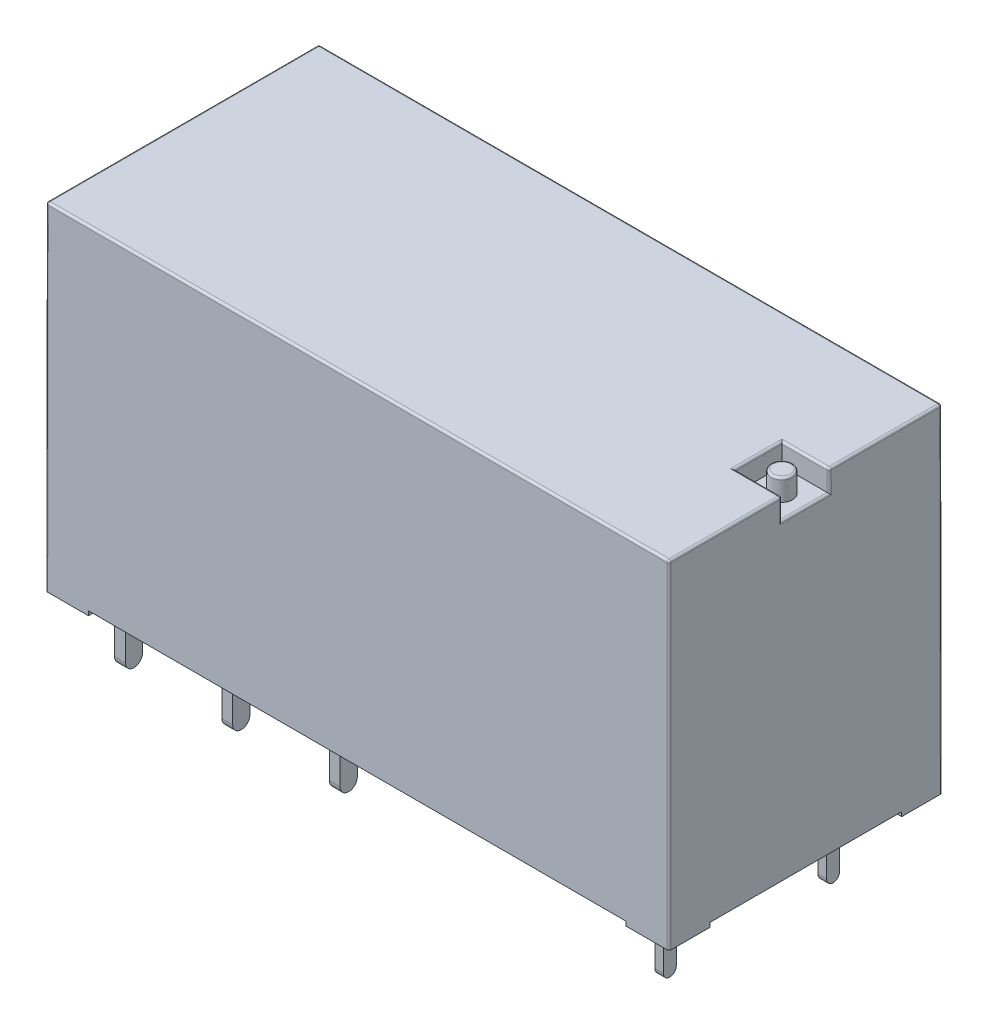
SolidWorks part; units mm, degrees
material "Custom Plastic"
ref_plane "Ebene vorne" through (0, 0, 0) normal (0, 0, 1) x (1, 0, 0)
ref_plane "Ebene oben" through (0, 0, 0) normal (0, 1, 0) x (1, 0, 0)
ref_plane "Ebene rechts" through (0, 0, 0) normal (1, 0, 0) x (0, 0, -1)
sketch "Sketch1" plane through (0, 0, 0) normal (0, 1, 0) x (1, 0, 0)
  line L1 (-14.5, 6.35) -> (14.5, 6.35)
  line L2 (-14.5, 6.35) -> (-14.5, -6.35)
  line L3 (-14.5, -6.35) -> (14.5, -6.35)
  line L4 (14.5, 6.35) -> (14.5, -6.35)
  line L5 (-14.5, 6.35) -> (14.5, -6.35) construction
  line L6 (-14.5, -6.35) -> (14.5, 6.35) construction
  point P0 (0, 0)
  dimension "D1" = 12.7
  dimension "D2" = 29
extrude "Boss-Extrude1" add sketch "Sketch1" against normal blind 15.7 draft 0.05 draft outward yes
sketch "Sketch2" plane through (0, -15.7, 0) normal (0, -1, 0) x (-1, 0, 0)
  line L0 (-14.5137, 0) -> (14.5137, 0) construction
  line L1 (-14.5137, -6.3637) -> (-14.5137, 6.3637) construction
  line L2 (14.5137, 6.3637) -> (14.5137, -6.3637) construction
  line L3 (0, 6.3637) -> (0, -6.3637) construction
  line L4 (14.0137, -5.8637) -> (12.5137, -5.8637)
  line L5 (14.0137, -5.8637) -> (14.0137, -4.4637)
  line L6 (14.0137, 5.8637) -> (12.5137, 5.8637)
  line L7 (-14.0137, -5.8637) -> (-14.0137, -4.4637)
  line L8 (14.0137, -5.8637) -> (-14.0137, 5.8637) construction
  line L9 (14.0137, 5.8637) -> (-14.0137, -5.8637) construction
  line L10 (-14.5137, 6.3637) -> (14.5137, 6.3637) construction
  line L11 (14.5137, -6.3637) -> (-14.5137, -6.3637) construction
  line L12 (14.0137, 4.4637) -> (14.5137, 4.4637)
  line L13 (14.5137, 4.4637) -> (14.5137, -4.4637)
  line L14 (14.5137, -4.4637) -> (14.0137, -4.4637)
  line L15 (14.0137, 4.4637) -> (14.0137, 5.8637)
  line L16 (12.5137, 6.3637) -> (12.5137, 5.8637)
  line L17 (12.5137, -5.8637) -> (12.5137, -6.3637)
  line L18 (-12.5137, 6.3637) -> (-12.5137, 5.8637)
  line L19 (-12.5137, -5.8637) -> (-12.5137, -6.3637)
  line L20 (-14.0137, 4.4637) -> (-14.5137, 4.4637)
  line L21 (-14.0137, -4.4637) -> (-14.5137, -4.4637)
  line L22 (-12.5137, 5.8637) -> (-14.0137, 5.8637)
  line L23 (12.5137, 6.3637) -> (-12.5137, 6.3637)
  line L24 (12.5137, -6.3637) -> (-12.5137, -6.3637)
  line L25 (-14.5137, -4.4637) -> (-14.5137, 4.4637)
  line L26 (-14.0137, 4.4637) -> (-14.0137, 5.8637)
  line L27 (-12.5137, -5.8637) -> (-14.0137, -5.8637)
  point P6 (0, 0)
  dimension "D1" = 0.5
  dimension "D2" = 0.5
  dimension "D3" = 1.9
  dimension "D4" = 2
extrude "Cut-Extrude1" cut sketch "Sketch2" against normal blind 0.2
sketch "Sketch3" plane through (0, -15.5, 0) normal (0, -1, 0) x (1, 0, 0)
  line L0 (-14.5135, 0) -> (14.5135, 0) construction
  line L1 (-14.5135, -4.4637) -> (-14.5135, 4.4637) construction
  line L2 (14.5135, 4.4637) -> (14.5135, -4.4637) construction
  line L3 (11.5863, 3.5) -> (11.9863, 4.1) construction
  line L4 (11.5863, -4.1) -> (11.9863, -4.1)
  line L5 (11.5863, -4.1) -> (11.5863, -3.5)
  line L6 (11.5863, -3.5) -> (11.9863, -3.5)
  line L7 (11.9863, -4.1) -> (11.9863, -3.5)
  line L8 (11.5863, -4.1) -> (11.9863, -3.5) construction
  line L9 (11.5863, -3.5) -> (11.9863, -4.1) construction
  line L10 (11.5863, 4.1) -> (11.9863, 3.5) construction
  line L11 (11.9863, 4.1) -> (11.9863, 3.5)
  line L12 (11.5863, 3.5) -> (11.9863, 3.5)
  line L13 (11.5863, 4.1) -> (11.5863, 3.5)
  line L14 (11.5863, 4.1) -> (11.9863, 4.1)
  line L15 (-14.5137, -6.3637) -> (-14.5137, -4.4637) construction
  line L16 (-8.4637, 3.4) -> (-7.9637, 3.4)
  line L17 (-8.4637, 3.4) -> (-8.4637, 4.2)
  line L18 (-8.4637, 4.2) -> (-7.9637, 4.2)
  line L19 (-7.9637, 3.4) -> (-7.9637, 4.2)
  line L20 (-8.4637, 3.4) -> (-7.9637, 4.2) construction
  line L21 (-8.4637, 4.2) -> (-7.9637, 3.4) construction
  line L22 (-13.4637, -4.2) -> (-12.9637, -4.2)
  line L23 (-13.4637, -4.2) -> (-13.4637, -3.4)
  line L24 (-13.4637, -3.4) -> (-12.9637, -3.4)
  line L25 (-12.9637, -4.2) -> (-12.9637, -3.4)
  line L26 (-13.4637, -4.2) -> (-12.9637, -3.4) construction
  line L27 (-13.4637, -3.4) -> (-12.9637, -4.2) construction
  line L28 (-13.4637, 3.4) -> (-12.9637, 4.2) construction
  line L29 (-13.4637, 4.2) -> (-12.9637, 3.4) construction
  line L30 (-12.9637, 4.2) -> (-12.9637, 3.4)
  line L31 (-13.4637, 3.4) -> (-12.9637, 3.4)
  line L32 (-13.4637, 4.2) -> (-13.4637, 3.4)
  line L33 (-13.4637, 4.2) -> (-12.9637, 4.2)
  line L34 (-8.4637, -4.2) -> (-7.9637, -3.4) construction
  line L35 (-8.4637, -3.4) -> (-7.9637, -4.2) construction
  line L36 (-7.9637, -3.4) -> (-7.9637, -4.2)
  line L37 (-8.4637, -4.2) -> (-7.9637, -4.2)
  line L38 (-8.4637, -3.4) -> (-8.4637, -4.2)
  line L39 (-8.4637, -3.4) -> (-7.9637, -3.4)
  line L40 (-8.2137, 3.4) -> (-8.2137, 4.2) construction
  line L41 (-2.9637, 4.2) -> (-3.4637, 3.4) construction
  line L42 (-2.9637, 3.4) -> (-3.4637, 4.2) construction
  line L43 (-2.9637, -3.4) -> (-3.4637, -4.2) construction
  line L44 (-2.9637, -4.2) -> (-3.4637, -3.4) construction
  line L45 (-2.9637, 4.2) -> (-3.4637, 4.2)
  line L46 (-2.9637, 4.2) -> (-2.9637, 3.4)
  line L47 (-2.9637, 3.4) -> (-3.4637, 3.4)
  line L48 (-3.4637, 4.2) -> (-3.4637, 3.4)
  line L49 (-3.4637, -4.2) -> (-3.4637, -3.4)
  line L50 (-2.9637, -3.4) -> (-3.4637, -3.4)
  line L51 (-2.9637, -4.2) -> (-2.9637, -3.4)
  line L52 (-2.9637, -4.2) -> (-3.4637, -4.2)
  point P6 (11.7863, -3.8)
  point P15 (11.7863, 3.8)
  point P16 (-8.2137, 3.8)
  point P21 (-13.2137, -3.8)
  point P32 (-13.2137, 3.8)
  point P37 (-8.2137, -3.8)
  point P48 (-3.2137, 3.8)
  point P49 (-3.2137, -3.8)
  dimension "D1" = 0.6
  dimension "D2" = 0.4
  dimension "D3" = 7.6
  dimension "D4" = 0.5
  dimension "D5" = 0.8
  dimension "D6" = 0.5
  dimension "D7" = 0.8
  dimension "D8" = 20
  dimension "D9" = 7.6
  dimension "D10" = 1.3
  dimension "D11" = 5
extrude "Boss-Extrude2" add sketch "Sketch3" along normal blind 3.8
fillet "Fillet1" radius 0.3 4 edges at (11.7863, -19.3, 4.1) (11.7863, -19.3, 3.5) (11.7863, -19.3, -3.5) (11.7863, -19.3, -4.1)
fillet "Fillet2" radius 0.4 12 edges at (-13.2137, -19.3, -4.2) (-13.2137, -19.3, -3.4) (-8.2137, -19.3, 4.2) (-8.2137, -19.3, 3.4) (-13.2137, -19.3, 3.4) (-13.2137, -19.3, 4.2) (-8.2137, -19.3, -4.2) (-8.2137, -19.3, -3.4) (-3.2137, -19.3, -4.2) (-3.2137, -19.3, -3.4) (-3.2137, -19.3, 3.4) (-3.2137, -19.3, 4.2)
sketch "Sketch4" plane through (0, 0, 0) normal (0, 1, 0) x (1, 0, 0)
  line L0 (14.5, 0) -> (-14.5, 0) construction
  line L1 (12.3, -1.1) -> (15.4821, -1.1)
  line L2 (12.3, -1.1) -> (12.3, 1.1)
  line L3 (12.3, 1.1) -> (15.4821, 1.1)
  line L4 (15.4821, -1.1) -> (15.4821, 1.1)
  line L5 (14.5, -6.35) -> (14.5, 6.35) construction
  line L6 (-14.5, 6.35) -> (-14.5, -6.35) construction
  circle A0 centre (13.4, 0) radius 0.5
  dimension "D3" = 1
  dimension "D1" = 2.2
  dimension "D2" = 2.2
  dimension "D4" = 1.1
extrude "Cut-Extrude2" cut sketch "Sketch4" against normal blind 1
fillet "Fillet3" radius 0.1 16 edges at (-14.5, 0, 0) (-14.5069, -7.85, -6.3569) (-14.5069, -7.85, 6.3569) (14.5069, -7.85, 6.3569) (14.5069, -7.85, -6.3569) (0, 0, -6.35) (14.5, 0, -3.725) (14.5009, -1, 0) (14.5004, -0.5, -1.1) (14.5004, -0.5, 1.1) (13.4, 0, 0.5) (13.4, 0, -1.1) (12.3, 0, 0) (13.4, 0, 1.1) (14.5, 0, 3.725) (0, 0, 6.35)
